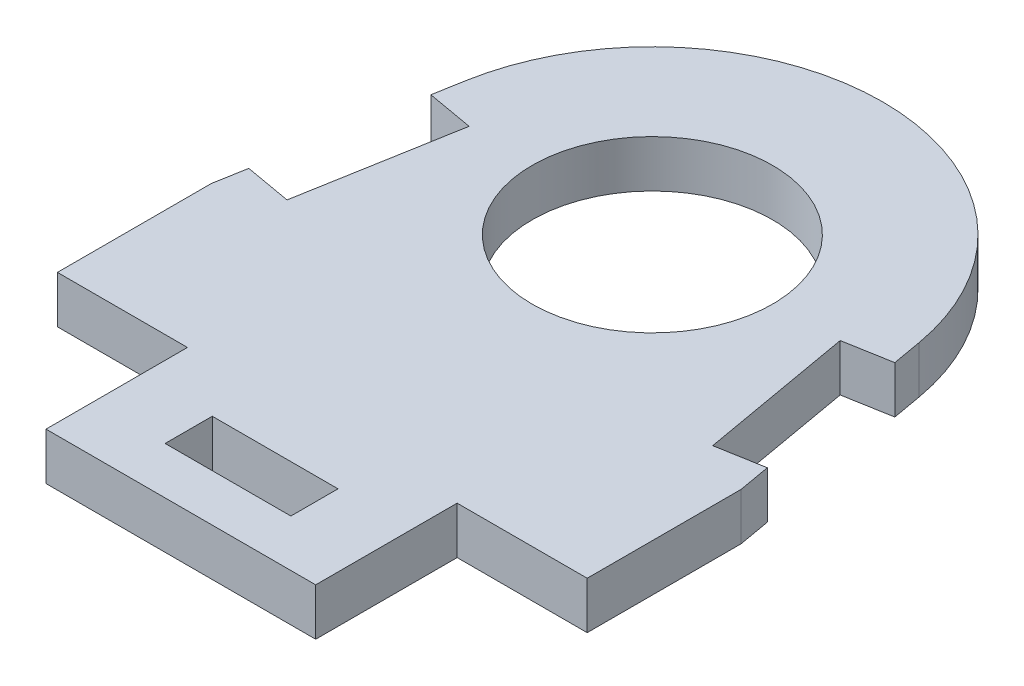
SolidWorks part; units mm, degrees
other "Markup1"
sketch "Sketch2" plane through (-16.8526, 1.5, -35.65) normal (0, 1, 0) x (1, 0, 0)
ref_plane "Front Plane" through (0, 0, 0) normal (0, 0, 1) x (1, 0, 0)
ref_plane "Top Plane" through (0, 0, 0) normal (0, 1, 0) x (1, 0, 0)
ref_plane "Right Plane" through (0, 0, 0) normal (1, 0, 0) x (0, 0, -1)
sketch "Sketch1" plane through (0, 0, 0) normal (0, 1, 0) x (1, 0, 0)
  line L0 (-18.5789, 0) -> (18.5789, 0)
  line L1 (18.5789, 0) -> (14.4274, 23.5439)
  line L2 (-18.5789, 0) -> (-14.4274, 23.5439)
  line L3 (14.7586, 21.6658) -> (16.4951, 11.8177)
  line L4 (14.7586, 21.6658) -> (11.8042, 21.1448)
  line L5 (16.4951, 11.8177) -> (13.5407, 11.2967)
  line L6 (11.8042, 21.1448) -> (13.5407, 11.2967)
  line L7 (-14.7586, 21.6658) -> (-16.4951, 11.8177)
  line L8 (-14.7586, 21.6658) -> (-11.8042, 21.1448)
  line L9 (-16.4951, 11.8177) -> (-13.5407, 11.2967)
  line L10 (-11.8042, 21.1448) -> (-13.5407, 11.2967)
  line L11 (-8.5789, 0) -> (-8.5789, -9)
  line L12 (-8.5789, -9) -> (8.5789, -9)
  line L13 (8.5789, -9) -> (8.5789, 0)
  line L14 (4, 0) -> (4, -3) construction
  line L15 (-4, -6) -> (4, -6)
  line L16 (-4, -6) -> (-4, -3)
  line L17 (-4, -3) -> (4, -3)
  line L18 (4, -6) -> (4, -3)
  line L19 (-4, -6) -> (4, -3) construction
  line L20 (-4, -3) -> (4, -6) construction
  line L21 (4, -6) -> (4, -9) construction
  line L22 (-16.8526, 0) -> (-16.8526, 9.7903)
  line L23 (16.8526, 0) -> (16.8526, 9.7903)
  circle A0 centre (0, 21) radius 7.65
  arc A1 (-14.4274, 23.5439) -> (14.4274, 23.5439) centre (0, 21) cw
  point P10 (0, 0)
  point P11 (0, 21)
  point P15 (0, -4.5)
  point P28 (0, -9)
  dimension "D2" = 15.3
  dimension "D3" = 7
  dimension "D1" = 21
  dimension "D4" = 80
  dimension "D5" = 3
  dimension "D6" = 10
  dimension "D7" = 12
  dimension "D8" = 12
  dimension "D9" = 3
  dimension "D10" = 10
  dimension "D11" = 8
  dimension "D12" = 1.7263
extrude "Boss-Extrude1" add sketch "Sketch1" along normal mid plane 3 contours A1 L2 L8 L10 L9 L0 L1 L5 L6 L4 A0 | L12 L13 L0 L11 L18 L15 L16 L17 region at (-16.362, 0, -4.8952) region at (0, 0, 0.1937)
ref_axis "Axis1" through (0, 0, -21) along (0, 1, 0)
